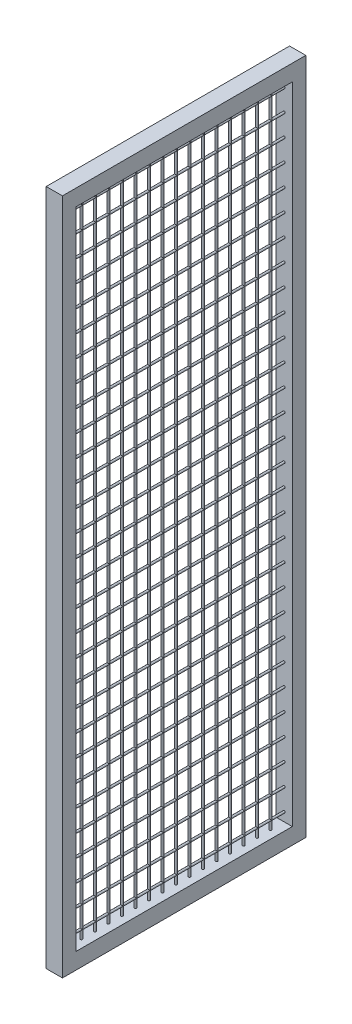
SolidWorks part; units mm, degrees
ref_plane "Piano frontale" through (0, 0, 0) normal (0, 0, 1) x (1, 0, 0)
ref_plane "Piano superiore" through (0, 0, 0) normal (0, 1, 0) x (1, 0, 0)
ref_plane "Piano destro" through (0, 0, 0) normal (1, 0, 0) x (0, 0, -1)
sketch "Schizzo1" plane through (0, 0, 1950) normal (0, 0, -1) x (-1, 0, 0)
  line L0 (-50, 2555) -> (-50, 50) construction
  line L1 (-30, 110) -> (30, 110)
  line L2 (-30, 110) -> (-30, 50)
  line L3 (-30, 50) -> (30, 50)
  line L4 (30, 110) -> (30, 50)
  line L5 (50, 2555) -> (50, 50) construction
  line L6 (-100, 50) -> (100, 50) construction
  line L7 (50, 2555) -> (-50, 2555) construction
  line L8 (-30, 2555) -> (30, 2555)
  line L9 (-30, 2555) -> (-30, 2495)
  line L10 (-30, 2495) -> (30, 2495)
  line L11 (30, 2555) -> (30, 2495)
  circle A0 centre (0, 2462.5) radius 3.75
  circle A1 centre (0, 2382.5) radius 3.75
  circle A2 centre (0, 2302.5) radius 3.75
  circle A3 centre (0, 2222.5) radius 3.75
  circle A4 centre (0, 2142.5) radius 3.75
  circle A5 centre (0, 2062.5) radius 3.75
  circle A6 centre (0, 1982.5) radius 3.75
  circle A7 centre (0, 1902.5) radius 3.75
  circle A8 centre (0, 1822.5) radius 3.75
  circle A9 centre (0, 1742.5) radius 3.75
  circle A10 centre (0, 1662.5) radius 3.75
  circle A11 centre (0, 1582.5) radius 3.75
  circle A12 centre (0, 1502.5) radius 3.75
  circle A13 centre (0, 1422.5) radius 3.75
  circle A14 centre (0, 1342.5) radius 3.75
  circle A15 centre (0, 1262.5) radius 3.75
  circle A16 centre (0, 1182.5) radius 3.75
  circle A17 centre (0, 1102.5) radius 3.75
  circle A18 centre (0, 1022.5) radius 3.75
  circle A19 centre (0, 942.5) radius 3.75
  circle A20 centre (0, 862.5) radius 3.75
  circle A21 centre (0, 782.5) radius 3.75
  circle A22 centre (0, 702.5) radius 3.75
  circle A23 centre (0, 622.5) radius 3.75
  circle A24 centre (0, 542.5) radius 3.75
  circle A25 centre (0, 462.5) radius 3.75
  circle A26 centre (0, 382.5) radius 3.75
  circle A27 centre (0, 302.5) radius 3.75
  circle A28 centre (0, 222.5) radius 3.75
  circle A29 centre (0, 142.5) radius 3.75
  dimension "D8" = 7.5
  dimension "D1" = 20
  dimension "D2" = 20
  dimension "D3" = 0
  dimension "D4" = 60
  dimension "D5" = 60
  dimension "D6" = 20
  dimension "D7" = 60
  dimension "D10" = 32.5
  dimension "D9" = 30
extrude "Estrusione-Estrusione1" add sketch "Schizzo1" along normal blind 900
sketch "Schizzo2" plane through (0, 110, 0) normal (0, 1, 0) x (1, 0, 0)
  line L1 (-30, -1050) -> (30, -1050)
  line L5 (30, -1050) -> (30, -1950) construction
  line L6 (-30, -1050) -> (-30, -1100)
  line L11 (-30, -1100) -> (30, -1100)
  line L16 (-30, -1050) -> (-30, -1950) construction
  line L17 (-30, -1950) -> (30, -1950)
  line L18 (-30, -1950) -> (-30, -1900)
  line L19 (-30, -1900) -> (30, -1900)
  line L20 (30, -1950) -> (30, -1900)
  line L21 (30, -1100) -> (30, -1050)
  line L22 (-30, -1950) -> (30, -1950) construction
  circle A44 centre (0, -1850) radius 3.75
  circle A45 centre (0, -1800) radius 3.75
  circle A46 centre (0, -1750) radius 3.75
  circle A47 centre (0, -1700) radius 3.75
  circle A48 centre (0, -1650) radius 3.75
  circle A49 centre (0, -1600) radius 3.75
  circle A50 centre (0, -1550) radius 3.75
  circle A51 centre (0, -1500) radius 3.75
  circle A52 centre (0, -1450) radius 3.75
  circle A53 centre (0, -1400) radius 3.75
  circle A54 centre (0, -1350) radius 3.75
  circle A55 centre (0, -1300) radius 3.75
  circle A56 centre (0, -1250) radius 3.75
  circle A57 centre (0, -1200) radius 3.75
  circle A58 centre (0, -1150) radius 3.75
  dimension "D3" = 50
  dimension "D5" = 15
  dimension "D1" = 50
  dimension "D2" = 60
  dimension "D8" = 0
  dimension "D4" = 50
extrude "Estrusione-Estrusione2" add sketch "Schizzo2" along normal up to surface (2385 mm away) up to face at (0, 2495, 1500)
